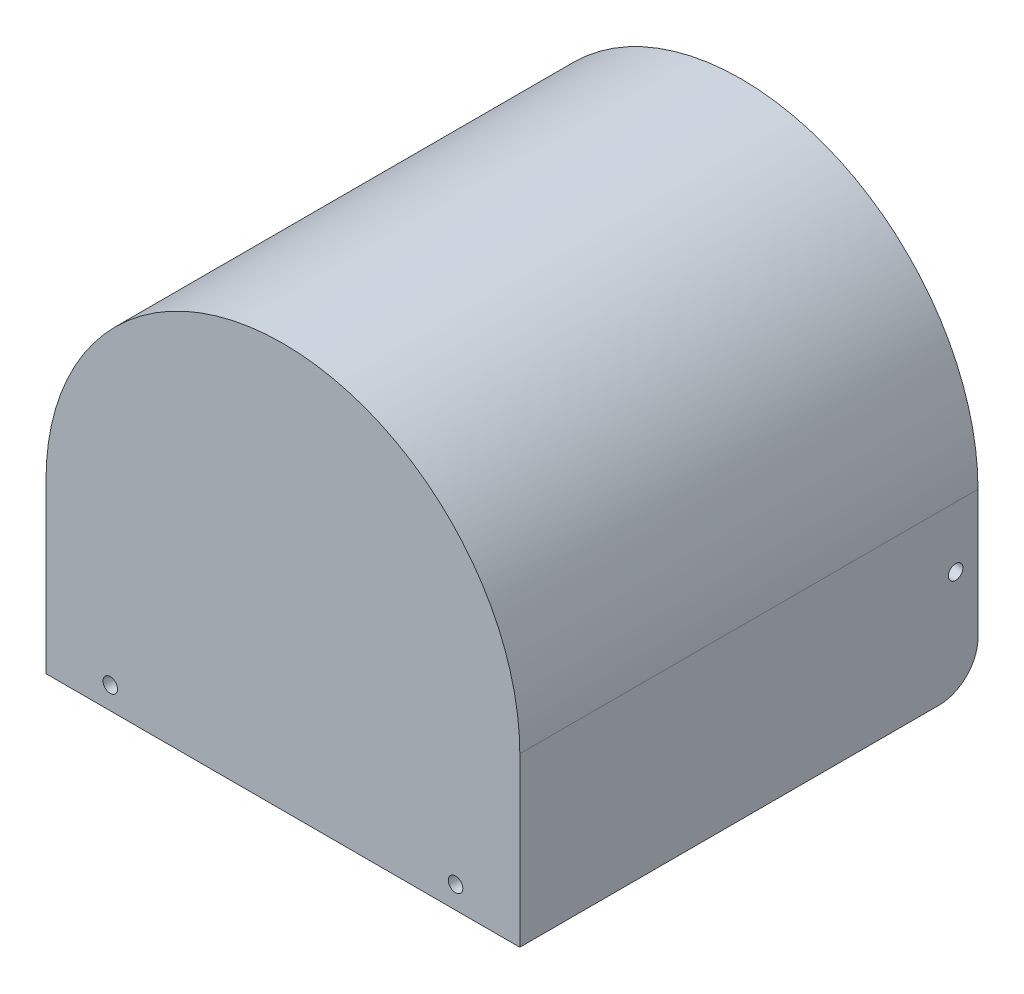
SolidWorks part; units mm, degrees
ref_plane "Front Plane" through (0, 0, 0) normal (0, 0, 1) x (1, 0, 0)
ref_plane "Top Plane" through (0, 0, 0) normal (0, 1, 0) x (1, 0, 0)
ref_plane "Right Plane" through (0, 0, 0) normal (1, 0, 0) x (0, 0, -1)
sketch "Sketch1" plane through (0, 0, 0) normal (0, 0, 1) x (1, 0, 0)
  line L0 (-40.4, 0) -> (-40.4, -30)
  line L1 (40.4, 0) -> (40.4, -30)
  line L2 (42.4, 0) -> (42.4, -30)
  line L3 (-42.4, 0) -> (-42.4, -30)
  line L4 (-42.4, -30) -> (-40.4, -30)
  line L5 (40.4, -30) -> (42.4, -30)
  arc A0 (-40.4, 0) -> (40.4, 0) centre (0, 0) cw
  arc A1 (-42.4, 0) -> (42.4, 0) centre (0, 0) cw
  dimension "D1" = 40.4
  dimension "D2" = 30
  dimension "D3" = 2
extrude "Boss-Extrude1" add sketch "Sketch1" along normal blind 82
sketch "Sketch2" plane through (0, 0, 0) normal (0, 1, 0) x (1, 0, 0)
  line L0 (-40.4, -82) -> (40.4, -82) construction
  line L1 (-40.4, -82) -> (40.4, -82)
  line L2 (-40.4, -82) -> (-40.4, -80)
  line L3 (-40.4, -80) -> (40.4, -80)
  line L4 (40.4, -82) -> (40.4, 0) construction
  line L5 (40.4, -80) -> (40.4, -82)
  dimension "D1" = 2
extrude "Boss-Extrude2" add sketch "Sketch2" against normal up to surface (30 mm away) and the other way up to surface up to face at (41.4, -30, 41) other way up to face at (0, 20.2, 41)
sketch "Sketch3" plane through (0, 0, 82) normal (0, 0, 1) x (1, 0, 0)
  line L0 (-42.4, -26) -> (42.4, -26) construction
  line L1 (-42.4, 0) -> (-42.4, -30) construction
  line L2 (42.4, -30) -> (42.4, 0) construction
  line L3 (-42.4, -30) -> (42.4, -30) construction
  line L4 (0, -26) -> (0, -30) construction
  circle A0 centre (-30.9, -26) radius 1.3
  circle A1 centre (30.9, -26) radius 1.3
  dimension "D3" = 2.6
  dimension "D1" = 4
  dimension "D2" = 61.8
extrude "Cut-Extrude1" cut sketch "Sketch3" against normal blind 10
sketch "Sketch4" plane through (42.4, 0, 0) normal (1, 0, 0) x (0, 0, -1)
  line L0 (-4, -30) -> (-4, 0) construction
  line L1 (-82, -30) -> (0, -30) construction
  line L2 (-82, 0) -> (0, 0) construction
  line L3 (0, -30) -> (0, 0) construction
  circle A0 centre (-4, -10.83) radius 1.3
  dimension "D2" = 2.6
  dimension "D1" = 4
  dimension "D3" = 19.17
extrude "Cut-Extrude2" cut sketch "Sketch4" against normal through all
fillet "Fillet1" radius 7 2 edges at (-41.4, -30, 0) (41.4, -30, 0)
